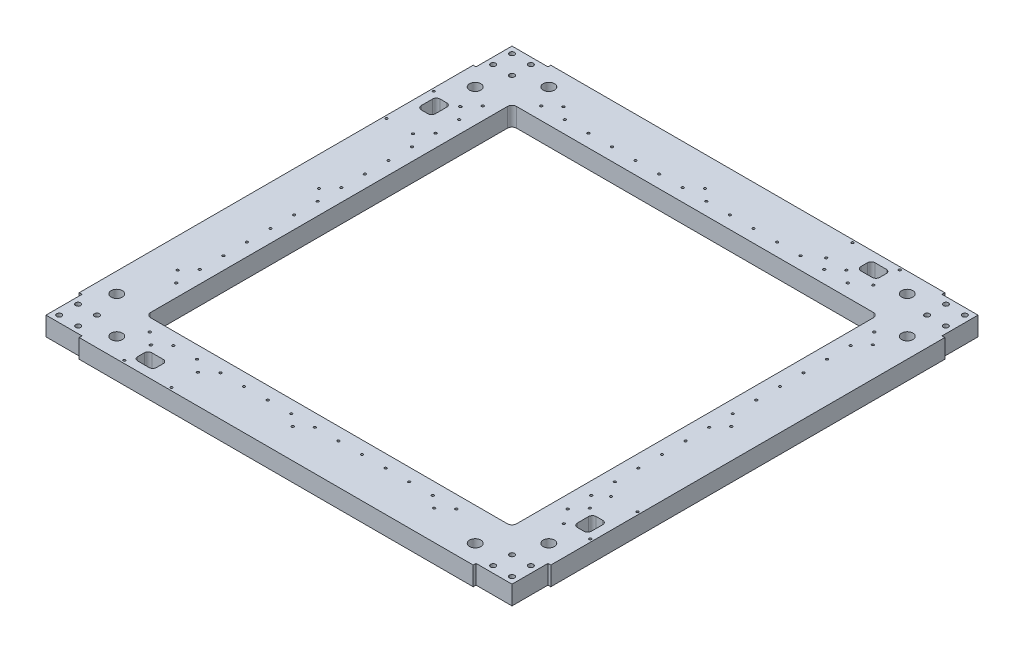
SolidWorks part; units mm, degrees
material "ASTM A36 Steel"
ref_plane "Front Plane" through (0, 0, 0) normal (0, 0, 1) x (1, 0, 0)
ref_plane "Top Plane" through (0, 0, 0) normal (0, 1, 0) x (1, 0, 0)
ref_plane "Right Plane" through (0, 0, 0) normal (1, 0, 0) x (0, 0, -1)
sketch "Sketch1" plane through (0, 0, 0) normal (0, 1, 0) x (1, 0, 0)
  line L1 (250, -250) -> (-250, -250)
  line L2 (250, -250) -> (250, 250)
  line L3 (250, 250) -> (-250, 250)
  line L4 (-250, -250) -> (-250, 250)
  line L5 (250, -250) -> (-250, 250) construction
  line L6 (250, 250) -> (-250, -250) construction
  point P0 (0, 0)
  dimension "D1" = 500
  dimension "D2" = 500
extrude "Boss-Extrude1" add sketch "Sketch1" along normal blind 20
sketch "Sketch2" plane through (0, 20, 0) normal (0, 1, 0) x (1, 0, 0)
  line L0 (250, 250) -> (-250, 250) construction
  line L10 (-250, 250) -> (-250, -250) construction
  line L15 (-250, 169) -> (-208, 169)
  line L16 (-250, 169) -> (-250, 211)
  line L17 (-174.5, 213.5) -> (-205.5, 213.5)
  line L27 (-250, 211) -> (-208, 211)
  line L33 (-208, 169) -> (-208, 211)
  line L35 (-250, 169) -> (-208, 211) construction
  line L36 (-250, 211) -> (-208, 169) construction
  line L37 (-169, 208) -> (-211, 208)
  line L38 (-169, 208) -> (-169, 250)
  line L39 (-169, 250) -> (-211, 250)
  line L40 (-211, 208) -> (-211, 250)
  line L41 (-169, 208) -> (-211, 250) construction
  line L42 (-169, 250) -> (-211, 208) construction
  line L43 (-208, 206) -> (-213, 211)
  line L44 (-174.5, 213.5) -> (-174.5, 244.5)
  line L45 (-174.5, 244.5) -> (-205.5, 244.5)
  line L46 (-205.5, 213.5) -> (-205.5, 244.5)
  line L47 (-174.5, 213.5) -> (-205.5, 244.5) construction
  line L48 (-174.5, 244.5) -> (-205.5, 213.5) construction
  line L49 (-213.5, 174.5) -> (-244.5, 174.5)
  line L50 (-213.5, 174.5) -> (-213.5, 205.5)
  line L51 (-213.5, 205.5) -> (-244.5, 205.5)
  line L52 (-244.5, 174.5) -> (-244.5, 205.5)
  line L53 (-213.5, 174.5) -> (-244.5, 205.5) construction
  line L54 (-213.5, 205.5) -> (-244.5, 174.5) construction
  line L55 (-206, 208) -> (-211, 213)
  line L56 (-213, 211) -> (-211, 213) construction
  point P1 (-229, 190)
  point P5 (-190, 229)
  point P23 (-229, 190)
  point P27 (-190, 229)
  dimension "D1" = 5
  dimension "D2" = 45
  dimension "D3" = 42
  dimension "D4" = 31
  dimension "D5" = 45
  dimension "D6" = 5
  dimension "D7" = 60
hole_wizard "M5 Clearance Hole1" positions "Sketch6" profile "Sketch7" hole size "M5" standard "ANSI Metric" end condition through all
sketch "Sketch6" plane through (0, 20, 0) normal (0, 1, 0) x (1, 0, 0)
  line L1 (-220, 220) -> (-240, 220) construction
  line L2 (-220, 220) -> (-220, 240) construction
  line L3 (-220, 240) -> (-240, 240) construction
  line L4 (-240, 220) -> (-240, 240) construction
  line L5 (-220, 220) -> (-240, 240) construction
  line L6 (-220, 240) -> (-240, 220) construction
  line L7 (250, 250) -> (-250, 250) construction
  line L8 (-250, 250) -> (-250, -250) construction
  point P2 (-240, 240)
  point P109 (-220, 220)
  point P110 (-220, 240)
  point P111 (-240, 220)
  dimension "D1" = 20
  dimension "D2" = 10
  dimension "D3" = 10
sketch "Sketch7" plane through (-240, 20, -240) normal (1, 0, 0) x (0, 0, 1)
  line L0 (0, 0) -> (0, 20)
  line L1 (0, 20) -> (2.65, 20)
  line L2 (2.65, 20) -> (2.65, 0)
  line L5 (2.65, 0) -> (0, 0)
  line L11 (0, -6.35) -> (0, 107.95) construction
  dimension "Thru Hole Dia." = 5.3
  dimension "Thru Hole Depth" = 20
hole_wizard "Bearing Press Fit" positions "Sketch8" profile "Sketch9" hole size "Ø12.0" standard "ANSI Metric" end condition through all
sketch "Sketch8" plane through (0, 20, 0) normal (0, 1, 0) x (1, 0, 0)
  line L1 (-169, 250) -> (-211, 208) construction
  point P8 (-190, 229)
  point P12 (-229, 190)
sketch "Sketch9" plane through (-190, 20, -229) normal (1, 0, 0) x (0, 0, 1)
  line L0 (0, 0) -> (0, 20)
  line L1 (0, 20) -> (6, 20)
  line L2 (6, 20) -> (6, 0)
  line L5 (6, 0) -> (0, 0)
  line L11 (0, -6.35) -> (0, 107.95) construction
  dimension "Thru Hole Dia." = 12
  dimension "Thru Hole Depth" = 20
ref_axis "Axis1" through (0, 8.4, 0) along (0, -1, 0)
pattern_circular "CirPattern1" count 4 over 360 about axis through (0, 8.4, 0) along (0, -1, 0) of "M5 Clearance Hole1", "Bearing Press Fit"
sketch "Sketch5" plane through (0, 20, 0) normal (0, 1, 0) x (1, 0, 0)
  line L1 (194, -194) -> (-194, -194)
  line L2 (194, -194) -> (194, 194)
  line L3 (194, 194) -> (-194, 194)
  line L4 (-194, -194) -> (-194, 194)
  line L5 (194, -194) -> (-194, 194) construction
  line L6 (194, 194) -> (-194, -194) construction
  point P0 (0, 0)
  dimension "D1" = 388
extrude "Cut-Extrude1" cut sketch "Sketch5" against normal up to surface (20 mm away) up to face at (-229, 0, 196)
sketch "Sketch10" plane through (0, 0, 0) normal (0, 1, 0) x (1, 0, 0)
  line L5 (194, 194) -> (-194, 194) construction
  line L6 (214, -214) -> (-214, -214)
  line L14 (214, -214) -> (214, 214)
  line L15 (214, 214) -> (-214, 214)
  line L16 (-214, -214) -> (-214, 214)
  line L17 (214, -214) -> (-214, 214) construction
  line L18 (214, 214) -> (-214, -214) construction
  line L19 (201.5, -201.5) -> (-201.5, -201.5)
  line L20 (201.5, -201.5) -> (201.5, 201.5)
  line L21 (201.5, 201.5) -> (-201.5, 201.5)
  line L22 (-201.5, -201.5) -> (-201.5, 201.5)
  line L23 (201.5, -201.5) -> (-201.5, 201.5) construction
  line L24 (201.5, 201.5) -> (-201.5, -201.5) construction
  point P0 (0, 0)
  point P6 (0, 0)
  dimension "D2" = 7.5
  dimension "D1" = 12.5
extrude "Linear Rail Slot" cut sketch "Sketch10" along normal blind 2.5
fillet "Fillet2" radius 5 4 edges at (-194, 10, 194) (194, 10, 194) (194, 10, -194) (-194, 10, -194)
sketch "Sketch11" plane through (0, 2.5, 0) normal (0, -1, 0) x (1, 0, 0)
  line L0 (-194, 207.5) -> (166, 207.5)
  line L1 (-201.5, 201.5) -> (201.5, 201.5) construction
  line L3 (-214, -214) -> (-214, 214) construction
  point P16 (148.5, 207.5)
  point P18 (123.5, 207.5)
  point P19 (98.5, 207.5)
  point P20 (73.5, 207.5)
  point P21 (48.5, 207.5)
  point P22 (23.5, 207.5)
  point P23 (-1.5, 207.5)
  point P24 (-26.5, 207.5)
  point P25 (-51.5, 207.5)
  point P26 (-76.5, 207.5)
  point P28 (-101.5, 207.5)
  point P29 (-126.5, 207.5)
  point P30 (-151.5, 207.5)
  point P31 (-176.5, 207.5)
  dimension "D1" = 360
  dimension "D2" = 6
  dimension "D4" = 14
  dimension "D5" = 25
  dimension "D6" = 20
  dimension "D3" = 17.5
hole_wizard "Tap Drill for M3x0.5 Tap1" positions "Sketch12" profile "Sketch13" hole size "M3x0.5" standard "ANSI Metric" end condition through all
sketch "Sketch12" plane through (0, 2.5, 0) normal (0, -1, 0) x (-1, 0, 0)
  line L0 (194, -207.5) -> (-166, -207.5) construction
  point P28 (-148.5, -207.5)
  point P31 (-123.5, -207.5)
  point P34 (-98.5, -207.5)
  point P37 (-73.5, -207.5)
  point P40 (-48.5, -207.5)
  point P43 (-23.5, -207.5)
  point P46 (1.5, -207.5)
  point P49 (26.5, -207.5)
  point P51 (51.5, -207.5)
  point P54 (76.5, -207.5)
  point P57 (101.5, -207.5)
  point P61 (126.5, -207.5)
  point P64 (151.5, -207.5)
  point P67 (176.5, -207.5)
sketch "Sketch13" plane through (148.5, 2.5, 207.5) normal (1, 0, 0) x (0, 0, -1)
  line L0 (0, 0) -> (0, 17.5)
  line L1 (0, 17.5) -> (1.25, 17.5)
  line L2 (1.25, 17.5) -> (1.25, 0)
  line L5 (1.25, 0) -> (0, 0)
  line L11 (0, -6.35) -> (0, 107.95) construction
  dimension "Thru Hole Dia." = 2.5
  dimension "Thru Hole Depth" = 17.5
sketch "Sketch14" plane through (0, 0, 0) normal (0, -1, 0) x (1, 0, 0)
  line L1 (-151.5, 213.5) -> (-176.5, 213.5)
  line L2 (-147.5, 217.5) -> (-147.5, 219.5)
  line L3 (-151.5, 223.5) -> (-176.5, 223.5)
  line L4 (-180.5, 217.5) -> (-180.5, 219.5)
  line L5 (-147.5, 213.5) -> (-180.5, 223.5) construction
  line L6 (-147.5, 223.5) -> (-180.5, 213.5) construction
  line L7 (-201.5, 201.5) -> (201.5, 201.5) construction
  line L8 (-176.5, 207.5) -> (-151.5, 207.5) construction
  line L19 (-1.5, 213.5) -> (-26.5, 213.5)
  line L25 (2.5, 217.5) -> (2.5, 219.5)
  line L26 (-1.5, 223.5) -> (-26.5, 223.5)
  line L31 (-30.5, 217.5) -> (-30.5, 219.5)
  line L32 (2.5, 213.5) -> (-30.5, 223.5) construction
  line L33 (2.5, 223.5) -> (-30.5, 213.5) construction
  line L34 (-26.5, 207.5) -> (-1.5, 207.5) construction
  line L35 (148.5, 213.5) -> (123.5, 213.5)
  line L36 (152.5, 217.5) -> (152.5, 219.5)
  line L37 (148.5, 223.5) -> (123.5, 223.5)
  line L38 (119.5, 217.5) -> (119.5, 219.5)
  line L39 (152.5, 213.5) -> (119.5, 223.5) construction
  line L40 (152.5, 223.5) -> (119.5, 213.5) construction
  line L41 (123.5, 207.5) -> (148.5, 207.5) construction
  arc A3 (-147.5, 219.5) -> (-151.5, 223.5) centre (-151.5, 219.5) ccw
  arc A4 (-151.5, 213.5) -> (-147.5, 217.5) centre (-151.5, 217.5) ccw
  arc A5 (-176.5, 213.5) -> (-180.5, 217.5) centre (-176.5, 217.5) cw
  arc A6 (-176.5, 223.5) -> (-180.5, 219.5) centre (-176.5, 219.5) ccw
  arc A7 (2.5, 219.5) -> (-1.5, 223.5) centre (-1.5, 219.5) ccw
  arc A8 (-1.5, 213.5) -> (2.5, 217.5) centre (-1.5, 217.5) ccw
  arc A9 (-26.5, 213.5) -> (-30.5, 217.5) centre (-26.5, 217.5) cw
  arc A10 (-26.5, 223.5) -> (-30.5, 219.5) centre (-26.5, 219.5) ccw
  arc A11 (152.5, 219.5) -> (148.5, 223.5) centre (148.5, 219.5) ccw
  arc A12 (148.5, 213.5) -> (152.5, 217.5) centre (148.5, 217.5) ccw
  arc A13 (123.5, 213.5) -> (119.5, 217.5) centre (123.5, 217.5) cw
  arc A14 (123.5, 223.5) -> (119.5, 219.5) centre (123.5, 219.5) ccw
  point P0 (-164, 218.5)
  point P12 (-164, 207.5)
  point P26 (-14, 218.5)
  point P45 (136, 218.5)
  dimension "D5" = 3
  dimension "D4" = 4
  dimension "D1" = 33
  dimension "D2" = 12
  dimension "D3" = 10
  dimension "D7" = 25
  dimension "D6" = 150
extrude "Cut-Extrude2" cut sketch "Sketch14" against normal offset from surface (3.5 mm away) 1 up to face at (148.5, 2.5, 206.25) offset beyond the face yes
hole_wizard "Tap Drill for M3x0.5 Tap2" positions "Sketch17" profile "Sketch18" hole size "M3x0.5" standard "ANSI Metric" end condition through all
sketch "Sketch17" plane through (0, 3.5, 0) normal (0, -1, 0) x (-1, 0, 0)
  point P0 (-136, -218.5)
  point P3 (14, -218.5)
  point P6 (164, -218.5)
sketch "Sketch18" plane through (136, 3.5, 218.5) normal (1, 0, 0) x (0, 0, -1)
  line L0 (0, 0) -> (0, 16.5)
  line L1 (0, 16.5) -> (1.25, 16.5)
  line L2 (1.25, 16.5) -> (1.25, 0)
  line L5 (1.25, 0) -> (0, 0)
  line L11 (0, -6.35) -> (0, 107.95) construction
  dimension "Thru Hole Dia." = 2.5
  dimension "Thru Hole Depth" = 16.5
mirror "Mirror5" about plane through (0, 0, 0) normal (0, 0, 1) of "Tap Drill for M3x0.5 Tap2", "Cut-Extrude2", "Tap Drill for M3x0.5 Tap1"
ref_plane "Plane1" through (0, 0, 0) normal (-0.7071, 0, 0.7071) x (0.7071, 0, 0.7071)
mirror "Mirror6" about plane through (0, 0, 0) normal (-0.7071, 0, 0.7071) of "Mirror5"
sketch "Sketch19" plane through (0, 2.5, 0) normal (0, -1, 0) x (1, 0, 0)
  line L0 (-198.5, 201.5) -> (-198.5, 214)
  line L1 (-201.5, 201.5) -> (201.5, 201.5) construction
  line L2 (-214, 214) -> (-178.4365, 214) construction
  line L3 (-198.5, 214) -> (-214, 214)
  line L4 (-214, 214) -> (-214, 198.5)
  line L5 (-214, 150.4365) -> (-214, 214) construction
  line L6 (-214, 198.5) -> (-201.5, 198.5)
  line L7 (-201.5, -201.5) -> (-201.5, 201.5) construction
  line L8 (-201.5, 198.5) -> (-201.5, 201.5)
  line L9 (-201.5, 201.5) -> (-198.5, 201.5)
  dimension "D1" = 3
extrude "Boss-Extrude2" add sketch "Sketch19" along normal up to surface (2.5 mm away) up to face at (-229, 0, 196)
sketch "Sketch20" plane through (0, 20, 0) normal (0, 1, 0) x (1, 0, 0)
  line L0 (250, -250) -> (250, 250) construction
  line L1 (247, -164) -> (219, -164) construction
  line L2 (247, -164) -> (247, -114) construction
  line L3 (247, -114) -> (219, -114) construction
  line L4 (219, -164) -> (219, -114) construction
  line L5 (247, -164) -> (219, -114) construction
  line L6 (247, -114) -> (219, -164) construction
  line L7 (-250, -250) -> (250, -250) construction
  line L13 (229.5, -160.3) -> (236.5, -160.3)
  line L14 (225.5, -156.3) -> (225.5, -144.3)
  line L15 (229.5, -140.3) -> (236.5, -140.3)
  line L16 (240.5, -156.3) -> (240.5, -144.3)
  line L17 (225.5, -160.3) -> (240.5, -140.3) construction
  line L18 (225.5, -140.3) -> (240.5, -160.3) construction
  arc A4 (229.5, -160.3) -> (225.5, -156.3) centre (229.5, -156.3) cw
  arc A5 (236.5, -160.3) -> (240.5, -156.3) centre (236.5, -156.3) ccw
  arc A6 (236.5, -140.3) -> (240.5, -144.3) centre (236.5, -144.3) cw
  arc A7 (225.5, -144.3) -> (229.5, -140.3) centre (229.5, -144.3) cw
  point P0 (233, -139)
  point P9 (233, -139)
  point P10 (233, -150.3)
  point P15 (0, 0)
  dimension "D7" = 13.7
  dimension "D8" = 4
  dimension "D1" = 28
  dimension "D2" = 50
  dimension "D3" = 17
  dimension "D4" = 86
  dimension "D5" = 15
  dimension "D6" = 20
hole_wizard "Tap Drill for M3x0.5 Tap3" positions "Sketch21" profile "Sketch22" hole size "M3x0.5" standard "ANSI Metric"
sketch "Sketch21" plane through (0, 20, 0) normal (0, 1, 0) x (1, 0, 0)
  point P0 (247, -114)
  point P3 (219, -114)
  point P6 (219, -164)
  point P9 (247, -164)
sketch "Sketch22" plane through (247, 20, 114) normal (1, 0, 0) x (0, 0, 1)
  line L0 (0, 0) -> (0, 10.7511)
  line L1 (0, 10.7511) -> (1.25, 10)
  line L2 (1.25, 10) -> (1.25, 0)
  line L5 (1.25, 0) -> (0, 0)
  line L10 (0, 10.7511) -> (-1.25, 10) construction
  line L11 (0, -6.35) -> (0, 107.95) construction
  dimension "Hole Dia." = 2.5
  dimension "Hole Depth" = 10
  dimension "Drill Angle" = 118
extrude "Cut-Extrude3" cut sketch "Sketch20" against normal through all
sketch "Sketch23" plane through (0, 20, 0) normal (0, 1, 0) x (1, 0, 0)
  line L0 (208.9, -250) -> (208.9, -247)
  line L1 (-250, -250) -> (250, -250) construction
  line L2 (208.9, -247) -> (247, -247)
  line L3 (247, -247) -> (247, -208.9)
  line L4 (247, -208.9) -> (250, -208.9)
  line L5 (250, -250) -> (250, 250) construction
  line L6 (250, -208.9) -> (250, -250)
  line L7 (208.9, -250) -> (250, -250)
  point P4 (250, -249.6623)
  dimension "D1" = 41.1
  dimension "D2" = 3
extrude "Cut-Extrude4" cut sketch "Sketch23" against normal up to surface (20 mm away) up to face at (233, 0, 150.3)
pattern_circular "CirPattern2" count 4 over 360 about axis through (0, 8.4, 0) along (0, -1, 0) of "Boss-Extrude2", "Tap Drill for M3x0.5 Tap3", "Cut-Extrude3", "Cut-Extrude4"
fillet "Fillet3" radius 4 40 edges at (150.4365, 1.25, 214) (121.5635, 1.25, 214) (0.4365, 1.25, 214) (-28.4365, 1.25, 214) (-178.4365, 1.25, 214) (-149.5635, 1.25, 214) (-214, 1.25, -149.5635) (-214, 1.25, -178.4365) (-214, 1.25, 0.4365) (-214, 1.25, -28.4365) (-214, 1.25, 150.4365) (-214, 1.25, 121.5635) (-149.5635, 1.25, -214) (-178.4365, 1.25, -214) (-28.4365, 1.25, -214) (0.4365, 1.25, -214) (121.5635, 1.25, -214) (150.4365, 1.25, -214) (214, 1.25, -149.5635) (214, 1.25, -178.4365) (214, 1.25, -28.4365) (214, 1.25, 0.4365) (214, 1.25, 121.5635) (214, 1.25, 150.4365) (198.5, 1.25, -214) (198.5, 1.25, -201.5) (214, 1.25, -198.5) (201.5, 1.25, -198.5) (214, 1.25, 198.5) (198.5, 1.25, 214) (198.5, 1.25, 201.5) (201.5, 1.25, 198.5) (-198.5, 1.25, 201.5) (-198.5, 1.25, 214) (-201.5, 1.25, 198.5) (-214, 1.25, 198.5) (-214, 1.25, -198.5) (-201.5, 1.25, -198.5) (-198.5, 1.25, -214) (-198.5, 1.25, -201.5)
